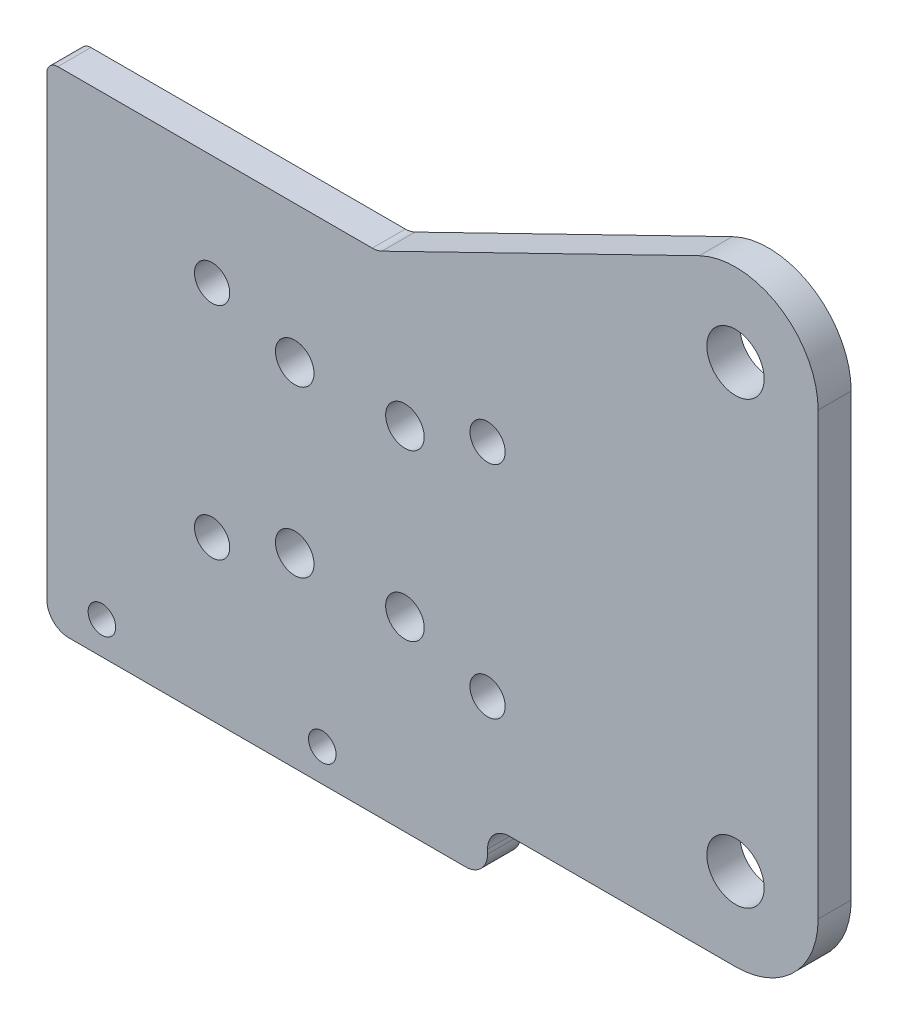
SolidWorks part; units mm, degrees
ref_plane "前视基准面" through (0, 0, 0) normal (0, 0, 1) x (1, 0, 0)
ref_plane "上视基准面" through (0, 0, 0) normal (0, 1, 0) x (1, 0, 0)
ref_plane "右视基准面" through (0, 0, 0) normal (1, 0, 0) x (0, 0, -1)
sketch "草图1" plane through (0, 0, 0) normal (0, 0, 1) x (1, 0, 0)
  line L0 (0, 0) -> (50000, 0) construction
  line L1 (-35, -27.5) -> (27.5, -27.5)
  line L2 (-35, -27.5) -> (-35, 27.5)
  line L3 (-35, 27.5) -> (27.5, 27.5)
  line L4 (35, -20) -> (35, 20)
  line L5 (-35, -27.5) -> (35, 27.5) construction
  line L6 (-35, 27.5) -> (35, -27.5) construction
  circle A0 centre (27.5, 20) radius 2.6
  circle A1 centre (27.5, -20) radius 2.6
  arc A4 (27.5, -27.5) -> (35, -20) centre (27.5, -20) ccw
  arc A5 (27.5, 27.5) -> (35, 20) centre (27.5, 20) cw
  point P0 (0, 0)
  dimension "D1" = 5.2
  dimension "D5" = 7.5
  dimension "D2" = 70
  dimension "60" = 55
  dimension "D3" = 40
  dimension "D4" = 7.5
extrude "凸台-拉伸1" add sketch "草图1" along normal blind 3
sketch "草图2" plane through (0, 0, 3) normal (0, 0, 1) x (1, 0, 0)
  line L0 (-35, 12.5) -> (-5, 12.5)
  line L1 (-35, 27.5) -> (-35, -27.5) construction
  line L2 (-5, 12.5) -> (24.2135, 26.7416)
  line L3 (-35, -27.5) -> (27.5, -27.5) construction
  line L4 (-35, 12.5) -> (-35, 37.5)
  line L5 (-35, 37.5) -> (27.5, 37.5)
  line L6 (27.5, 37.5) -> (27.5, 27.5)
  circle A0 centre (27.5, 20) radius 7.5 construction
  arc A1 (24.2135, 26.7416) -> (27.5, 27.5) centre (27.5, 20) cw
  dimension "D1" = 15
  dimension "D4" = 10
  dimension "D2" = 40
  dimension "D3" = 30
extrude "切除-拉伸1" cut sketch "草图2" against normal blind 3
sketch "草图3" plane through (0, 0, 3) normal (0, 0, 1) x (1, 0, 0)
  line L0 (-35, 12.5) -> (-35, -27.5) construction
  line L1 (-20, -17.5) -> (5, -17.5) construction
  line L2 (-20, -17.5) -> (-20, 2.5) construction
  line L3 (-20, 2.5) -> (5, 2.5) construction
  line L4 (5, -17.5) -> (5, 2.5) construction
  line L5 (-20, -17.5) -> (5, 2.5) construction
  line L6 (-20, 2.5) -> (5, -17.5) construction
  line L7 (-20, -7.5) -> (5, -7.5) construction
  line L8 (-35, -27.5) -> (27.5, -27.5) construction
  line L9 (-7.5, 2.5) -> (-7.5, -17.5) construction
  circle A0 centre (-20, 2.5) radius 1.6
  circle A2 centre (5, 2.5) radius 1.6
  circle A3 centre (5, -17.5) radius 1.6
  circle A4 centre (-20, -17.5) radius 1.6
  circle A5 centre (27.5, 20) radius 15 construction
  circle A6 centre (27.5, -20) radius 15 construction
  point P0 (-7.5, -7.5)
  dimension "D4" = 3.2
  dimension "D5" = 10
  dimension "D6" = 30
  dimension "D7" = 30
  dimension "D1" = 20
  dimension "D2" = 25
  dimension "D3" = 15
extrude "切除-拉伸2" cut sketch "草图3" against normal blind 3
fillet "圆角1" radius 1 2 edges at (-35, -27.5, 1.5) (-35, 12.5, 1.5)
sketch "草图4" plane through (0, 0, 3) normal (0, 0, 1) x (1, 0, 0)
  line L0 (-20, 2.5) -> (5, -17.5) construction
  line L1 (5, 2.5) -> (-20, -17.5) construction
  line L3 (-12.5, -15) -> (-2.5, -15) construction
  line L4 (-12.5, -15) -> (-12.5, 0) construction
  line L5 (-12.5, 0) -> (-2.5, 0) construction
  line L6 (-2.5, -15) -> (-2.5, 0) construction
  line L7 (-12.5, -15) -> (-2.5, 0) construction
  line L8 (-12.5, 0) -> (-2.5, -15) construction
  circle A0 centre (-2.5, 0) radius 1.75
  circle A1 centre (-12.5, 0) radius 1.75
  circle A2 centre (-12.5, -15) radius 1.75
  circle A3 centre (-2.5, -15) radius 1.75
  point P8 (-7.5, -7.5)
  dimension "D3" = 3.5
  dimension "D4" = 3.5
  dimension "D5" = 3.5
  dimension "D6" = 3.5
  dimension "D1" = 15
  dimension "D2" = 10
extrude "切除-拉伸3" cut sketch "草图4" against normal blind 10
sketch "草图5" plane through (0, 0, 0) normal (0, 0, -1) x (-1, 0, 0)
  line L0 (34, -27.5) -> (-27.5, -27.5) construction
  line L1 (35, -26.5) -> (-5, -26.5)
  line L2 (35, -26.5) -> (35, -31.9)
  line L3 (35, -31.9) -> (-5, -31.9)
  line L4 (-5, -26.5) -> (-5, -31.9)
  dimension "D1" = 40
  dimension "D2" = 4.4
extrude "凸台-拉伸2" add sketch "草图5" against normal up to surface (3 mm away) up to face at (-0.75, -15, 3)
sketch "草图6" plane through (0, 0, 0) normal (0, 0, -1) x (-1, 0, 0)
  line L0 (-5, -31.9) -> (35, -31.9) construction
  line L1 (35, 11.5) -> (35, -31.9) construction
  circle A0 centre (30, -28.95) radius 1.25
  circle A1 centre (10, -28.95) radius 1.25
  dimension "D1" = 2.95
  dimension "D2" = 5
  dimension "D4" = 2.5
  dimension "D3" = 2
extrude "切除-拉伸4" cut sketch "草图6" against normal blind 4
fillet "圆角2" radius 2 4 edges at (-35, -31.9, 1.5) (-5, 12.5, 1.5) (5, -27.5, 1.5) (5, -31.9, 1.5)
